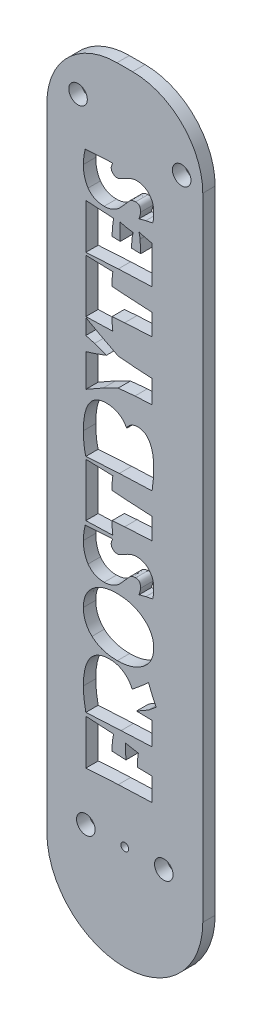
SolidWorks part; units mm, degrees
material "Pine"
ref_plane "Front" through (0, 0, 0) normal (0, 0, 1) x (1, 0, 0)
ref_plane "Top" through (0, 0, 0) normal (0, 1, 0) x (1, 0, 0)
ref_plane "Right" through (0, 0, 0) normal (1, 0, 0) x (0, 0, -1)
sketch "Sketch2" plane through (0, 0, 0) normal (0, 0, 1) x (1, 0, 0)
  line L1 (-20, -100) -> (20, -100)
  line L2 (-20, -100) -> (-20, 100)
  line L3 (-20, 100) -> (20, 100)
  line L4 (20, -100) -> (20, 100)
  line L5 (-20, -100) -> (20, 100) construction
  line L6 (-20, 100) -> (20, -100) construction
  point P1 (0, 0)
  dimension "D1" = 200
  dimension "D2" = 40
extrude "Boss-Extrude1" add sketch "Sketch2" along normal blind 3.175
sketch "Sketch3" plane through (0, 0, 0) normal (0, 0, -1) x (-1, 0, 0)
  line L0 (20, -100) -> (-20, -100) construction
  line L1 (1.325, -88.5019) -> (-1.325, -88.5019)
  arc A0 (-1.325, -88.5019) -> (1.325, -88.5019) centre (0, -90) ccw
  dimension "D1" = 4
  dimension "D2" = 10
  dimension "D3" = 2.65
fillet "Fillet1" radius 20 2 edges at (20, -100, 1.5875) (-20, -100, 1.5875)
fillet "Fillet2" radius 18 2 edges at (20, 100, 1.5875) (-20, 100, 1.5875)
sketch "Sketch7" plane through (0, 0, 3.175) normal (0, 0, 1) x (1, 0, 0)
  line L0 (-30.4029, 88) -> (30.4029, 88) construction
  line L1 (-12, 88) -> (14.5898, 83.3115) construction
  circle A0 centre (-12, 88) radius 2.38
  circle A3 centre (14.5898, 83.3115) radius 2.38
  point P4 (0, 88)
  dimension "D2" = 4.76
  dimension "D3" = 12
  dimension "D7" = 4.76
  dimension "D5" = 10
  dimension "D6" = 27
extrude "Cut-Extrude5" cut sketch "Sketch7" against normal through all
sketch "Sketch8" plane through (0, 0, 3.175) normal (0, 0, 1) x (1, 0, 0)
  line L0 (0, -90) -> (0, -49.3452) construction
  line L1 (-10, -73.25) -> (0, -73.25) construction
  line L2 (0, -73.25) -> (10, -73.25) construction
  circle A12 centre (0, -73.25) radius 1
  circle A13 centre (10, -73.25) radius 2.38
  circle A14 centre (-10, -73.25) radius 2.38
  dimension "D2" = 4.76
  dimension "D14" = 2
  dimension "D3" = 4.76
  dimension "D4" = 10
  dimension "D5" = 10
extrude "Cut-Extrude6" cut sketch "Sketch8" against normal through all
sketch "Sketch9" plane through (0, 0, 3.175) normal (0, 0, 1) x (1, 0, 0)
  line L0 (0, -100) -> (0, 100) construction
  line L1 (2, 100) -> (-2, 100) construction
  line L2 (7, -75) -> (7, 75) construction
  line L3 (7, 0) -> (0, 0) construction
  text T0 "   FROSTBYTES" font "Showcard Gothic" height 17
  dimension "D2" = 90
  dimension "D1" = 150
  dimension "D3" = 7
extrude "Cut-Extrude8" cut sketch "Sketch9" against normal blind 10 body kept at (-20, 82, 0)
